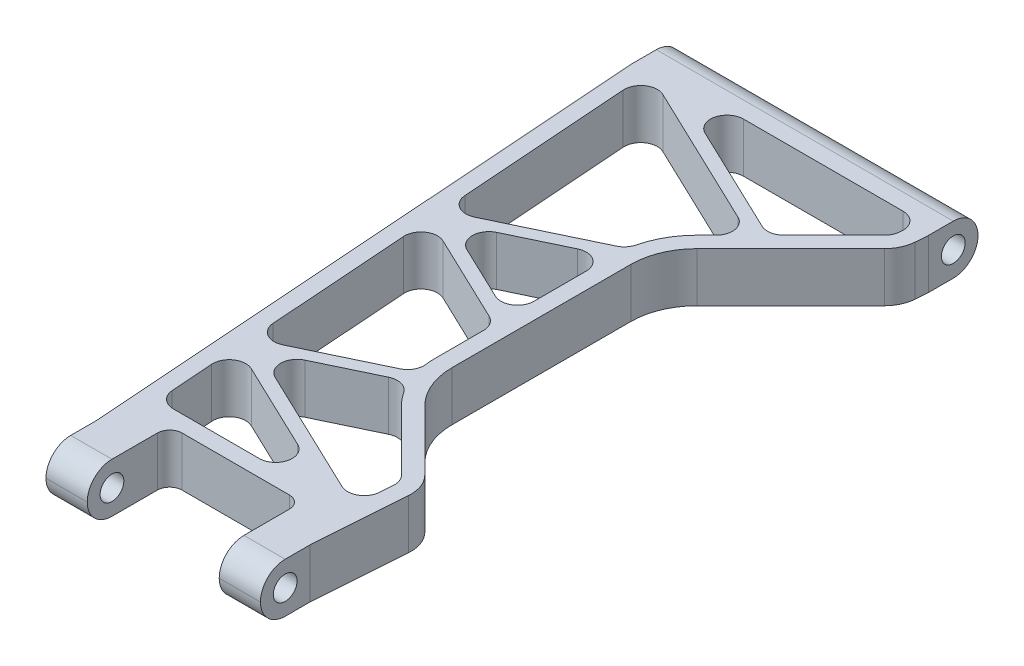
SolidWorks part; units mm, degrees
ref_plane "Front Plane" through (0, 0, 0) normal (0, 0, 1) x (1, 0, 0)
ref_plane "Top Plane" through (0, 0, 0) normal (0, 1, 0) x (1, 0, 0)
ref_plane "Right Plane" through (0, 0, 0) normal (1, 0, 0) x (0, 0, -1)
sketch "Sketch1" plane through (0, 0, 0) normal (0, 1, 0) x (1, 0, 0)
  line L0 (0, 0) -> (0, -120.65) construction
  line L1 (-28.575, 0) -> (28.575, 0) construction
  line L2 (-28.575, 4.7625) -> (-28.575, -4.7625)
  line L3 (28.575, 4.7625) -> (28.575, -4.7625)
  line L4 (-20.6375, -120.65) -> (20.6375, -120.65) construction
  line L5 (-20.6375, -115.8875) -> (-20.6375, -125.4125)
  line L6 (20.6375, -115.8875) -> (20.6375, -125.4125)
  line L7 (-28.575, -4.7625) -> (-20.6375, -115.8875)
  line L8 (28.575, -4.7625) -> (20.6375, -115.8875)
  line L9 (-20.6375, -125.4125) -> (20.6375, -125.4125)
  line L11 (-12.7, -125.4125) -> (-12.7, -109.5375)
  line L12 (-12.7, -109.5375) -> (12.7, -109.5375)
  line L13 (-28.575, 4.7625) -> (28.575, 4.7625)
  line L14 (-28.575, -4.7625) -> (28.575, -4.7625)
  line L15 (-20.6375, -115.8875) -> (20.6375, -115.8875)
  line L16 (-19.05, 4.7625) -> (-19.05, -4.7625)
  line L17 (-19.05, -4.7625) -> (19.05, -4.7625)
  line L18 (19.05, -4.7625) -> (19.05, 4.7625)
  line L19 (12.7, -109.5375) -> (12.7, -125.4125)
  line L23 (28.2348, -9.525) -> (4.7625, -32.9973)
  line L24 (4.7625, -32.9973) -> (4.7625, -77.9009)
  line L25 (4.7625, -77.9009) -> (22.1116, -95.25)
  point P6 (0, 0)
  point P9 (-28.575, 0)
  point P11 (28.575, 0)
  point P16 (0, -120.65)
  point P18 (-20.6375, -120.65)
  point P21 (20.6375, -120.65)
  dimension "D1" = 9.525
  dimension "D2" = 57.15
  dimension "D3" = 9.525
  dimension "D4" = 41.275
  dimension "D5" = 120.65
  dimension "D6" = 7.9375
  dimension "D7" = 7.9375
  dimension "D8" = 9.525
  dimension "D9" = 9.525
  dimension "D10" = 15.875
  dimension "D13" = 9.525
  dimension "D14" = 9.525
  dimension "D15" = 25.4
  dimension "D16" = 45
  dimension "D17" = 45
extrude "Boss-Extrude1" add sketch "Sketch1" along normal blind 9.525 contours L16 L13 L2 L14 | L18 L14 L3 L13 | L7 L15 L8 L14 | L15 L5 L9 | L15 L19 L9 L6 | L14 L18 L13 L16 region at (-23.8125, 0, 0) region at (-5.339, 0, 56.6599) region at (0, 0, 0) region at (-16.6687, 0, 120.65) region at (23.8125, 0, 0) region at (16.6687, 0, 120.65)
sketch "Sketch6" plane through (-28.575, 0, 0) normal (-1, 0, 0) x (0, 0, 1)
  line L0 (-4.7625, 9.525) -> (-4.7625, 0) construction
  line L1 (115.8875, 9.525) -> (125.4125, 9.525) construction
  circle A0 centre (0, 4.7625) radius 2.286
  circle A1 centre (120.65, 4.7625) radius 2.286
  point P2 (-4.7625, 4.7625)
  point P3 (0, 0)
  point P10 (120.65, 9.525)
  dimension "D1" = 4.572
extrude "Cut-Extrude2" cut sketch "Sketch6" against normal through all both and the other way through all
fillet "Fillet5" radius 4.7625 6 edges at (0, 0, -4.7625) (0, 9.525, -4.7625) (16.6687, 0, 125.4125) (-16.6687, 0, 125.4125) (-16.6687, 9.525, 125.4125) (16.6687, 9.525, 125.4125)
fillet "Fillet6" radius 12.7 2 edges at (4.7625, 4.7625, 77.9009) (4.7625, 4.7625, 32.9973)
fillet "Fillet7" radius 6.35 2 edges at (28.2348, 4.7625, 9.525) (22.1116, 4.7625, 95.25)
sketch "Sketch7" plane through (0, 0, 0) normal (0, -1, 0) x (1, 0, 0)
  line L0 (-17.4625, 115.7743) -> (-25.4, 4.6493)
  line L1 (-25.4, 4.6493) -> (-25.4, 3.175)
  line L2 (-25.4, 3.175) -> (25.4, 3.175)
  line L3 (25.4, 3.175) -> (25.4, 4.6493)
  line L4 (25.4, 4.6493) -> (25.2367, 6.936)
  line L5 (24.3148, 8.9549) -> (6.2372, 27.0325)
  line L6 (1.5875, 38.2578) -> (1.5875, 72.6404)
  line L7 (6.2372, 83.8657) -> (17.8162, 95.4447)
  line L8 (18.7381, 97.916) -> (17.4625, 115.7743)
  line L9 (17.4625, 115.7743) -> (17.4625, 117.475)
  line L10 (17.4625, 117.475) -> (15.875, 117.475)
  line L11 (15.875, 117.475) -> (15.875, 106.3625)
  line L12 (18.1348, 106.3625) -> (-18.1348, 106.3625)
  line L13 (-15.875, 106.3625) -> (-15.875, 117.475)
  line L14 (-15.875, 117.475) -> (-17.4625, 117.475)
  line L15 (-17.4625, 117.475) -> (-17.4625, 115.7743)
  line L16 (28.575, 4.7625) -> (28.4036, 7.1623)
  line L17 (26.5599, 11.2) -> (8.4822, 29.2776)
  line L18 (4.7625, 38.2578) -> (4.7625, 72.6404)
  line L19 (8.4822, 81.6206) -> (20.0613, 93.1997)
  line L20 (21.905, 98.1422) -> (20.6375, 115.8875)
  line L21 (20.6375, 115.8875) -> (20.6375, 120.65)
  line L22 (20.6375, 120.65) -> (12.7, 120.65)
  line L23 (12.7, 120.65) -> (12.7, 109.5375)
  line L24 (12.7, 109.5375) -> (-12.7, 109.5375)
  line L25 (-12.7, 109.5375) -> (-12.7, 120.65)
  line L26 (-12.7, 120.65) -> (-20.6375, 120.65)
  line L27 (-20.6375, 120.65) -> (-20.6375, 115.8875)
  line L28 (-20.6375, 115.8875) -> (-28.575, 4.7625)
  line L29 (-28.575, 4.7625) -> (-28.575, 0)
  line L30 (-28.575, 0) -> (28.575, 0)
  line L31 (28.575, 0) -> (28.575, 4.7625)
  line L32 (28.575, 4.7625) -> (28.4036, 7.1623)
  line L33 (26.5599, 11.2) -> (8.4822, 29.2776)
  line L34 (4.7625, 38.2578) -> (4.7625, 72.6404)
  line L35 (8.4822, 81.6206) -> (20.0613, 93.1997)
  line L36 (21.905, 98.1422) -> (20.6375, 115.8875)
  line L37 (20.6375, 115.8875) -> (20.6375, 120.65)
  line L38 (20.6375, 120.65) -> (12.7, 120.65)
  line L39 (12.7, 120.65) -> (12.7, 109.5375)
  line L40 (12.7, 109.5375) -> (-12.7, 109.5375)
  line L41 (-12.7, 109.5375) -> (-12.7, 120.65)
  line L42 (-12.7, 120.65) -> (-20.6375, 120.65)
  line L43 (-20.6375, 120.65) -> (-20.6375, 115.8875)
  line L44 (-20.6375, 115.8875) -> (-28.575, 4.7625)
  line L45 (-28.575, 4.7625) -> (-28.575, 0)
  line L46 (-28.575, 0) -> (28.575, 0)
  line L47 (28.575, 0) -> (28.575, 4.7625)
  line L48 (15.875, 106.3625) -> (-15.875, 106.3625) construction
  line L52 (25.2624, 6.5762) -> (24.2493, 20.7586)
  line L53 (-8.6192, 3.175) -> (22.0954, 3.175)
  line L54 (19.7143, 23.3975) -> (-9.9873, 9.2151)
  line L55 (25.2624, 6.5762) -> (24.2493, 20.7586)
  line L56 (-8.6192, 3.175) -> (22.0954, 3.175)
  line L57 (19.7143, 23.3975) -> (-9.9873, 9.2151)
  line L58 (-14.3942, 92.1494) -> (2.722, 100.3224)
  line L59 (-18.3454, 103.4137) -> (-18.9292, 95.2408)
  line L60 (1.354, 106.3625) -> (-15.1785, 106.3625)
  line L61 (-14.3942, 92.1494) -> (2.722, 100.3224)
  line L62 (-18.3454, 103.4137) -> (-18.9292, 95.2408)
  line L63 (1.354, 106.3625) -> (-15.1785, 106.3625)
  line L64 (16.6746, 65.9531) -> (-13.4912, 51.5491)
  line L65 (23.34, 33.4888) -> (21.2096, 63.3142)
  line L66 (-13.4912, 45.8188) -> (18.805, 30.3975)
  line L67 (16.6746, 65.9531) -> (-13.4912, 51.5491)
  line L68 (23.34, 33.4888) -> (21.2096, 63.3142)
  line L69 (-13.4912, 45.8188) -> (18.805, 30.3975)
  line L70 (15.0629, 29.5455) -> (-18.1426, 45.401)
  line L71 (-20.4877, 6.84) -> (15.0629, 23.8153)
  line L72 (-22.6777, 42.7621) -> (-25.0227, 9.9313)
  line L73 (15.0629, 29.5455) -> (-18.1426, 45.401)
  line L74 (-20.4877, 6.84) -> (15.0629, 23.8153)
  line L75 (-22.6777, 42.7621) -> (-25.0227, 9.9313)
  line L76 (19.5036, 76.2025) -> (19.5036, 100.9369)
  line L77 (-10.652, 85.5673) -> (14.9605, 73.3374)
  line L78 (15.0893, 103.5889) -> (-10.652, 91.2975)
  line L79 (19.5036, 76.2025) -> (19.5036, 100.9369)
  line L80 (-10.652, 85.5673) -> (14.9605, 73.3374)
  line L81 (15.0893, 103.5889) -> (-10.652, 91.2975)
  line L82 (12.0232, 72.1011) -> (-15.3035, 85.1495)
  line L83 (-17.2333, 52.401) -> (12.0232, 66.3709)
  line L84 (-19.8385, 82.5106) -> (-21.7684, 55.4923)
  line L85 (12.0232, 72.1011) -> (-15.3035, 85.1495)
  line L86 (-17.2333, 52.401) -> (12.0232, 66.3709)
  line L87 (-19.8385, 82.5106) -> (-21.7684, 55.4923)
  arc A0 (25.2367, 6.936) -> (24.3148, 8.9549) centre (22.0697, 6.7098) ccw
  arc A1 (1.5875, 38.2578) -> (6.2372, 27.0325) centre (17.4625, 38.2578) ccw
  arc A2 (6.2372, 83.8657) -> (1.5875, 72.6404) centre (17.4625, 72.6404) ccw
  arc A3 (17.8162, 95.4447) -> (18.7381, 97.916) centre (15.5712, 97.6898) ccw
  arc A4 (28.4036, 7.1623) -> (26.5599, 11.2) centre (22.0697, 6.7098) ccw
  arc A5 (4.7625, 38.2578) -> (8.4822, 29.2776) centre (17.4625, 38.2578) ccw
  arc A6 (8.4822, 81.6206) -> (4.7625, 72.6404) centre (17.4625, 72.6404) ccw
  arc A7 (20.0613, 93.1997) -> (21.905, 98.1422) centre (15.5712, 97.6898) ccw
  arc A8 (28.4036, 7.1623) -> (26.5599, 11.2) centre (22.0697, 6.7098) ccw
  arc A9 (4.7625, 38.2578) -> (8.4822, 29.2776) centre (17.4625, 38.2578) ccw
  arc A10 (8.4822, 81.6206) -> (4.7625, 72.6404) centre (17.4625, 72.6404) ccw
  arc A11 (20.0613, 93.1997) -> (21.905, 98.1422) centre (15.5712, 97.6898) ccw
  arc A15 (-18.9292, 95.2408) -> (-14.3942, 92.1494) centre (-15.7622, 95.0146) ccw
  arc A16 (22.0954, 3.175) -> (25.2624, 6.5762) centre (22.0954, 6.35) ccw
  arc A17 (22.0954, 3.175) -> (25.2624, 6.5762) centre (22.0954, 6.35) ccw
  arc A18 (-9.9873, 9.2151) -> (-8.6192, 3.175) centre (-8.6192, 6.35) ccw
  arc A19 (24.2493, 20.7586) -> (19.7143, 23.3975) centre (21.0824, 20.5324) ccw
  arc A22 (-9.9873, 9.2151) -> (-8.6192, 3.175) centre (-8.6192, 6.35) ccw
  arc A23 (24.2493, 20.7586) -> (19.7143, 23.3975) centre (21.0824, 20.5324) ccw
  arc A24 (-15.1785, 106.3625) -> (-18.3454, 103.4137) centre (-15.1785, 103.1875) ccw
  arc A25 (2.722, 100.3224) -> (1.354, 106.3625) centre (1.354, 103.1875) ccw
  arc A26 (-18.9292, 95.2408) -> (-14.3942, 92.1494) centre (-15.7622, 95.0146) ccw
  arc A27 (-15.1785, 106.3625) -> (-18.3454, 103.4137) centre (-15.1785, 103.1875) ccw
  arc A28 (2.722, 100.3224) -> (1.354, 106.3625) centre (1.354, 103.1875) ccw
  arc A29 (21.2096, 63.3142) -> (16.6746, 65.9531) centre (18.0427, 63.088) ccw
  arc A30 (18.805, 30.3975) -> (23.34, 33.4888) centre (20.1731, 33.2626) ccw
  arc A31 (-13.4912, 51.5491) -> (-13.4912, 45.8188) centre (-12.1231, 48.6839) ccw
  arc A32 (21.2096, 63.3142) -> (16.6746, 65.9531) centre (18.0427, 63.088) ccw
  arc A33 (18.805, 30.3975) -> (23.34, 33.4888) centre (20.1731, 33.2626) ccw
  arc A34 (-13.4912, 51.5491) -> (-13.4912, 45.8188) centre (-12.1231, 48.6839) ccw
  arc A35 (15.0629, 23.8153) -> (15.0629, 29.5455) centre (13.6948, 26.6804) ccw
  arc A36 (-25.0227, 9.9313) -> (-20.4877, 6.84) centre (-21.8558, 9.7051) ccw
  arc A37 (-18.1426, 45.401) -> (-22.6777, 42.7621) centre (-19.5107, 42.5359) ccw
  arc A38 (15.0629, 23.8153) -> (15.0629, 29.5455) centre (13.6948, 26.6804) ccw
  arc A39 (-25.0227, 9.9313) -> (-20.4877, 6.84) centre (-21.8558, 9.7051) ccw
  arc A40 (-18.1426, 45.401) -> (-22.6777, 42.7621) centre (-19.5107, 42.5359) ccw
  arc A41 (12.0232, 66.3709) -> (12.0232, 72.1011) centre (10.6551, 69.236) ccw
  arc A42 (14.9605, 73.3374) -> (19.5036, 76.2025) centre (16.3286, 76.2025) ccw
  arc A43 (-10.652, 91.2975) -> (-10.652, 85.5673) centre (-9.2839, 88.4324) ccw
  arc A44 (19.1082, 102.4713) -> (15.0893, 103.5889) centre (16.4574, 100.7238) ccw
  arc A45 (19.5036, 100.9369) -> (19.1082, 102.4713) centre (16.3286, 100.9369) ccw
  arc A46 (14.9605, 73.3374) -> (19.5036, 76.2025) centre (16.3286, 76.2025) ccw
  arc A47 (-10.652, 91.2975) -> (-10.652, 85.5673) centre (-9.2839, 88.4324) ccw
  arc A48 (19.1082, 102.4713) -> (15.0893, 103.5889) centre (16.4574, 100.7238) ccw
  arc A49 (19.5036, 100.9369) -> (19.1082, 102.4713) centre (16.3286, 100.9369) ccw
  arc A50 (-21.7684, 55.4923) -> (-17.2333, 52.401) centre (-18.6014, 55.2661) ccw
  arc A51 (-15.3035, 85.1495) -> (-19.8385, 82.5106) centre (-16.6715, 82.2844) ccw
  arc A52 (12.0232, 66.3709) -> (12.0232, 72.1011) centre (10.6551, 69.236) ccw
  arc A53 (-21.7684, 55.4923) -> (-17.2333, 52.401) centre (-18.6014, 55.2661) ccw
  arc A54 (-15.3035, 85.1495) -> (-19.8385, 82.5106) centre (-16.6715, 82.2844) ccw
  dimension "D1" = 0
  dimension "D2" = 3.175
  dimension "D3" = 0
  dimension "D4" = 0
  dimension "D5" = 0
  dimension "D6" = 0
  dimension "D7" = 0
  dimension "D8" = 0
extrude "Cut-Extrude3" cut sketch "Sketch7" against normal through all both and the other way through all contours L61 A28 L12 A27 L0 A26 | L8 A48 L81 A47 L80 A2 L7 A3 | L85 A54 L0 A53 L86 L6 A2 | L67 A34 L69 L6 | L73 A40 L0 A39 L74 L5 A1 | L57 A22 L2 L4 A0 L5 region at (-8.9411, 0, 100.5717) region at (-10.9452, 0, 68.7843) region at (-11.1459, 0, 25.9624) region at (3.9109, 0, 91.514) region at (-4.9076, 0, 48.6839) region at (7.8249, 0, 9.3024)
fillet "Fillet8" radius 3.175 9 edges at (2.1468, 4.7625, 76.8171) (1.5875, 4.7625, 61.3879) (2.9491, 4.7625, 79.0728) (18.3558, 4.7625, 103.2687) (1.7642, 4.7625, 35.8956) (11.267, 4.7625, 22.0027) (1.5875, 4.7625, 58.7491) (1.5875, 4.7625, 38.6188) (13.0529, 4.7625, 20.2167)
fillet "Fillet9" radius 2.3813 2 edges at (12.7, 4.7625, 109.5375) (-12.7, 4.7625, 109.5375)
